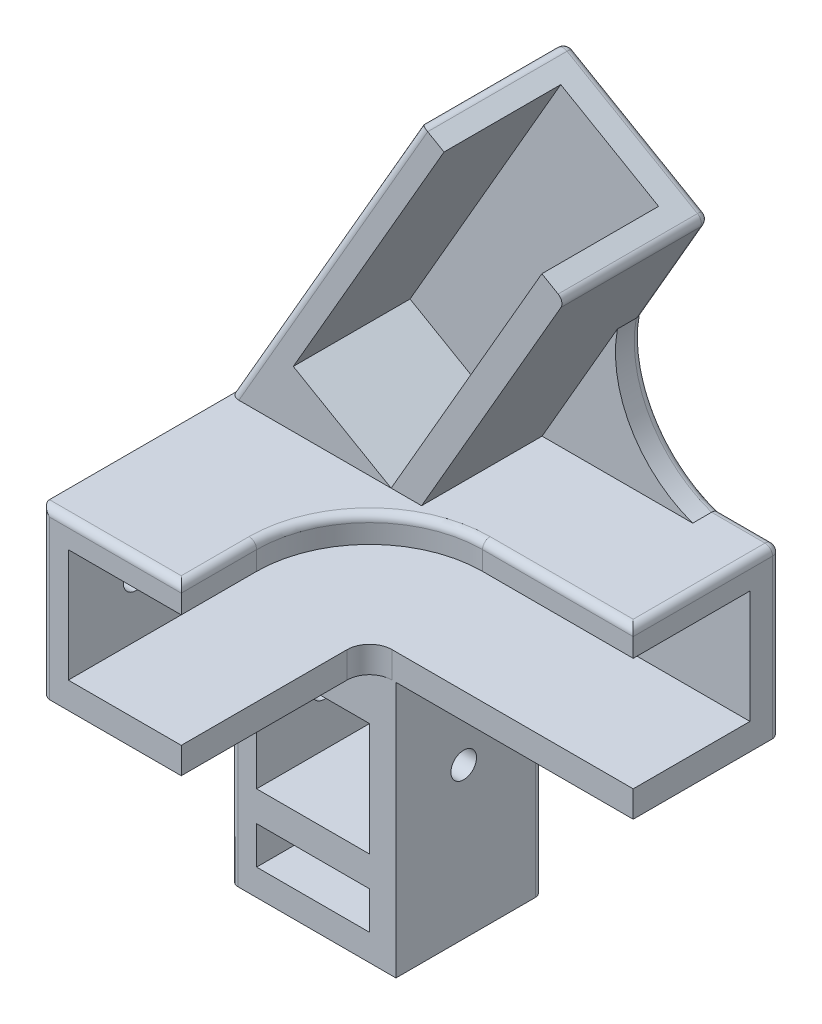
SolidWorks part; units mm, degrees
ref_plane "Front Plane" through (0, 0, 0) normal (0, 0, 1) x (1, 0, 0)
ref_plane "Top Plane" through (0, 0, 0) normal (0, 1, 0) x (1, 0, 0)
ref_plane "Right Plane" through (0, 0, 0) normal (1, 0, 0) x (0, 0, -1)
sketch "Sketch1" plane through (0, 0, 0) normal (0, 0, 1) x (1, 0, 0)
  line L1 (-5.6994, 32.9163) -> (16.3006, 32.9163)
  line L2 (-5.6994, 10.9163) -> (-5.6994, -23.0837)
  line L3 (-5.6994, -23.0837) -> (16.3006, -23.0837)
  line L4 (16.3006, 32.9163) -> (16.3006, -23.0837)
  line L5 (-5.6994, 10.9163) -> (-37.1994, 10.9163)
  line L7 (-5.6994, 32.9163) -> (-37.1994, 32.9163)
  line L8 (-37.1994, 10.9163) -> (-37.1994, 32.9163)
  dimension "D1" = 22
  dimension "D2" = 22
  dimension "D3" = 56
  dimension "D4" = 53.5
extrude "Boss-Extrude1" add sketch "Sketch1" along normal blind 19.5
sketch "Sketch3" plane through (0, 0, 19.5) normal (0, 0, 1) x (1, 0, 0)
  line L1 (16.3006, 32.9163) -> (-2.1994, 32.9163)
  line L2 (16.3006, 32.9163) -> (16.3006, 10.9163)
  line L3 (16.3006, 10.9163) -> (-2.1994, 10.9163)
  line L4 (-2.1994, 32.9163) -> (-2.1994, 10.9163)
  dimension "D1" = 18.5
extrude "Boss-Extrude2" add sketch "Sketch3" along normal blind 25
sketch "Sketch5" plane through (0, 0, 44.5) normal (0, 0, 1) x (1, 0, 0)
  line L0 (-37.1994, 32.9163) -> (-37.1994, 10.9163) construction
  line L1 (-37.1994, 29.4163) -> (12.8006, 29.4163)
  line L2 (-37.1994, 29.4163) -> (-37.1994, 14.4163)
  line L3 (-37.1994, 14.4163) -> (12.8006, 14.4163)
  line L4 (12.8006, 29.4163) -> (12.8006, 14.4163)
  line L5 (16.3006, 10.9163) -> (16.3006, 32.9163) construction
  line L6 (-2.1994, 4.4163) -> (12.8006, 4.4163)
  line L7 (-2.1994, 4.4163) -> (-2.1994, -10.5837)
  line L8 (-2.1994, -10.5837) -> (12.8006, -10.5837)
  line L9 (12.8006, 4.4163) -> (12.8006, -10.5837)
  line L12 (-2.1994, 32.9163) -> (-37.1994, 32.9163) construction
  line L13 (-2.1994, 10.9163) -> (16.3006, 10.9163) construction
  line L15 (16.3006, -23.0837) -> (16.3006, 10.9163) construction
  line L16 (-5.6994, -23.0837) -> (16.3006, -23.0837) construction
  line L17 (-2.1994, -14.5837) -> (12.8006, -14.5837)
  line L18 (-2.1994, -14.5837) -> (-2.1994, -19.5837)
  line L19 (-2.1994, -19.5837) -> (12.8006, -19.5837)
  line L20 (12.8006, -14.5837) -> (12.8006, -19.5837)
  dimension "D1" = 3.5
  dimension "D2" = 6.5
  dimension "D3" = 15
  dimension "D4" = 3.5
  dimension "D5" = 15
  dimension "D6" = 15
  dimension "D7" = 3.5
  dimension "D8" = 15
  dimension "D9" = 4
  dimension "D10" = 3.5
extrude "Cut-Extrude1" cut sketch "Sketch5" against normal offset from surface (40.5 mm away) 4 up to face at (-8.8661, 6.9163, 0)
sketch "Sketch7" plane through (16.3006, 0, 0) normal (1, 0, 0) x (0, 0, -1)
  line L0 (-34.5, 10.9163) -> (-19.5, 10.9163)
  line L1 (-44.5, 10.9163) -> (-19.5, 10.9163) construction
  line L2 (-19.5, 10.9163) -> (-19.5, -4.0837)
  line L3 (-19.5, -23.0837) -> (-19.5, 10.9163) construction
  arc A0 (-34.5, 10.9163) -> (-19.5, -4.0837) centre (-34.5, -4.0837) cw
  dimension "D1" = 15
extrude "Boss-Extrude4" add sketch "Sketch7" against normal blind 3.5
sketch "Sketch8" plane through (0, 0, 0) normal (0, 0, -1) x (-1, 0, 0)
  line L0 (5.6994, 10.9163) -> (20.6994, 10.9163)
  line L1 (37.1994, 10.9163) -> (5.6994, 10.9163) construction
  line L2 (5.6994, 10.9163) -> (5.6994, -4.0837)
  line L3 (5.6994, 10.9163) -> (5.6994, -23.0837) construction
  arc A0 (20.6994, 10.9163) -> (5.6994, -4.0837) centre (20.6994, -4.0837) ccw
  dimension "D1" = 15
extrude "Boss-Extrude5" add sketch "Sketch8" against normal blind 3.5
sketch "Sketch9" plane through (0, 32.9163, 0) normal (0, 1, 0) x (1, 0, 0)
  line L0 (-2.1994, -34.5) -> (-2.1994, -19.5)
  line L1 (-2.1994, -44.5) -> (-2.1994, -19.5) construction
  line L2 (-2.1994, -19.5) -> (-17.1994, -19.5)
  line L3 (-2.1994, -19.5) -> (-37.1994, -19.5) construction
  arc A0 (-2.1994, -34.5) -> (-17.1994, -19.5) centre (-17.1994, -34.5) ccw
  dimension "D1" = 15
extrude "Boss-Extrude6" add sketch "Sketch9" against normal blind 3.5
fillet "Fillet3" radius 3 1 edges
sketch "Sketch11" plane through (0, 0, 0) normal (0, 0, -1) x (-1, 0, 0)
  line L0 (1.1994, -23.0837) -> (1.1994, 10.9163) construction
  line L2 (5.6994, -23.0837) -> (-16.3006, -23.0837) construction
  line L5 (5.6994, -4.0837) -> (5.6994, -23.0837) construction
  text T0 "MR.3" font "Century Gothic" height 12
  dimension "D1" = 4.5
extrude "Cut-Extrude3" cut sketch "Sketch11" against normal blind 1
sketch "Sketch12" plane through (0, 0, 0) normal (0, 0, -1) x (-1, 0, 0)
  line L0 (37.1994, 21.9163) -> (-16.3006, 21.9163) construction
  line L1 (37.1994, 32.9163) -> (37.1994, 10.9163) construction
  line L2 (-16.3006, -23.0837) -> (-16.3006, 32.9163) construction
  line L3 (-12.8006, 14.4163) -> (-12.8006, 29.4163) construction
  circle A0 centre (-5.3006, 21.9163) radius 1.7
  circle A1 centre (10.9494, 21.9163) radius 1.7
  circle A2 centre (27.1994, 21.9163) radius 1.7
  dimension "D4" = 3.4
  dimension "D1" = 7.5
  dimension "D2" = 10
  dimension "D3" = 16.25
extrude "Cut-Extrude4" cut sketch "Sketch12" against normal blind 5
sketch "Sketch13" plane through (-5.6994, 0, 0) normal (-1, 0, 0) x (0, 0, 1)
  line L0 (4, 4.4163) -> (19.5, 4.4163) construction
  line L1 (19.5, 10.9163) -> (19.5, -23.0837) construction
  circle A0 centre (10.5, -3.0837) radius 1.7
  dimension "D2" = 9
  dimension "D3" = 3.4
  dimension "D1" = 7.5
extrude "Cut-Extrude5" cut sketch "Sketch13" against normal blind 45
sketch "Sketch14" plane through (16.3006, 0, 0) normal (1, 0, 0) x (0, 0, -1)
  line L0 (-10.5, -3.0837) -> (-10.5, 32.9163) construction
  line L1 (-44.5, 32.9163) -> (0, 32.9163) construction
  line L2 (-44.5, 21.9163) -> (-10.5, 21.9163) construction
  line L3 (-44.5, 10.9163) -> (-44.5, 32.9163) construction
  circle A0 centre (-10.5, 21.9163) radius 1.7
  circle A1 centre (-35.5, 21.9163) radius 1.7
  dimension "D1" = 3.4
  dimension "D2" = 9
extrude "Cut-Extrude6" cut sketch "Sketch14" against normal blind 45
sketch "Sketch15" plane through (0, -23.0837, 0) normal (0, -1, 0) x (1, 0, 0)
  line L0 (16.3006, 9.75) -> (-5.6994, 9.75) construction
  line L1 (16.3006, 19.5) -> (16.3006, 0) construction
  line L2 (-5.6994, 19.5) -> (-5.6994, 0) construction
  line L3 (5.3006, 19.5) -> (5.3006, 0) construction
  line L4 (-5.6994, 19.5) -> (16.3006, 19.5) construction
  line L5 (-5.6994, 0) -> (16.3006, 0) construction
  circle A0 centre (5.3006, 9.75) radius 1.7
  dimension "D1" = 3.4
extrude "Cut-Extrude7" cut sketch "Sketch15" against normal blind 4
mirror "Mirror2" about plane through (16.3006, 32.9163, 19.5) normal (-1, 0, 0) of "Cut-Extrude7", "Cut-Extrude6", "Cut-Extrude5", "Cut-Extrude4", "Fillet3", "Boss-Extrude6", "Boss-Extrude5", "Boss-Extrude4", "Cut-Extrude1", "Boss-Extrude2", "Boss-Extrude1"
sketch "Sketch16" plane through (0, 0, 0) normal (0, 0, -1) x (-1, 0, 0)
  line L0 (-69.8006, 32.9163) -> (37.1994, 32.9163) construction
  line L1 (-16.3006, 32.9163) -> (53.9943, 32.9163)
  line L2 (-16.3006, 32.9163) -> (-16.3006, -24.95)
  line L3 (-16.3006, -24.95) -> (53.9943, -24.95)
  line L4 (53.9943, 32.9163) -> (53.9943, -24.95)
extrude "Cut-Extrude8" cut sketch "Sketch16" against normal blind 72
sketch "Sketch20" plane through (0, 0, 0) normal (0, 0, -1) x (-1, 0, 0)
  line L0 (-20.8006, -23.0837) -> (-20.8006, 10.9163) construction
  line L1 (-16.3006, -23.0837) -> (-38.3006, -23.0837) construction
  line L2 (-16.3006, 32.9163) -> (-16.3006, -23.0837) construction
  text T0 "MR.3" font "Century Gothic" height 12
  dimension "D1" = 4.5
extrude "Cut-Extrude9" cut sketch "Sketch20" against normal blind 1
sketch "Sketch21" plane through (0, 0, 0) normal (0, 0, -1) x (-1, 0, 0)
  line L0 (-16.3006, 32.9163) -> (-41.6514, 76.8252)
  line L1 (-41.6514, 76.8252) -> (-60.704, 65.8252)
  line L2 (-60.704, 65.8252) -> (-41.704, 32.9163)
  line L3 (-69.8006, 32.9163) -> (-16.3006, 32.9163) construction
  line L4 (-41.704, 32.9163) -> (-16.3006, 32.9163)
  dimension "D1" = 22
  dimension "D2" = 60
  dimension "D3" = 38
extrude "Boss-Extrude7" add sketch "Sketch21" against normal up to surface (19.5 mm away) up to face at (57.3006, 31.1663, 19.5)
sketch "Sketch22" plane through (0, 0, 19.5) normal (0, 0, 1) x (1, 0, 0)
  line L0 (44.6825, 75.0752) -> (24.6722, 40.4163)
  line L1 (60.704, 65.8252) -> (41.6514, 76.8252) construction
  line L2 (24.6722, 40.4163) -> (37.6625, 32.9163)
  line L3 (37.6625, 32.9163) -> (57.6729, 67.5752)
  line L4 (57.6729, 67.5752) -> (44.6825, 75.0752)
  line L5 (41.6514, 76.8252) -> (16.3006, 32.9163) construction
  line L7 (16.3006, 32.9163) -> (41.704, 32.9163) construction
  dimension "D1" = 15
  dimension "D2" = 3.5
extrude "Cut-Extrude10" cut sketch "Sketch22" against normal up to surface (15.5 mm away) up to face at (41.8506, 21.9163, 4)
sketch "Sketch23" plane through (0, 0, 0) normal (0, 0, -1) x (-1, 0, 0)
  line L0 (-61.704, 32.9163) -> (-41.704, 32.9163)
  line L1 (-69.8006, 32.9163) -> (-41.704, 32.9163) construction
  line L2 (-41.704, 32.9163) -> (-51.704, 50.2368)
  line L3 (-60.704, 65.8252) -> (-41.704, 32.9163) construction
  arc A0 (-61.704, 32.9163) -> (-51.704, 50.2368) centre (-66.8048, 47.4082) ccw
  dimension "D1" = 20
extrude "Boss-Extrude8" add sketch "Sketch23" against normal blind 3.5
fillet "Fillet4" radius 1 22 edges at (16.3006, 10.9163, 39.5) (16.3006, 6.5229, 23.8934) (61.5506, 10.9163, 0) (42.694, 6.5229, 0) (34.8006, 32.9163, 39.5) (53.4997, 39.7265, 0) (28.976, 54.8707, 0) (16.3006, -13.5837, 19.5) (16.3006, 4.9163, 0) (38.3006, -13.5837, 0) (69.8006, 32.9163, 9.75) (69.8006, 21.9163, 0) (16.3006, 21.9163, 44.5) (39.194, 32.9163, 23.8934) (25.5506, 32.9163, 44.5) (41.6514, 76.8252, 9.75) (51.1777, 71.3252, 0) (60.704, 65.8252, 9.75)
